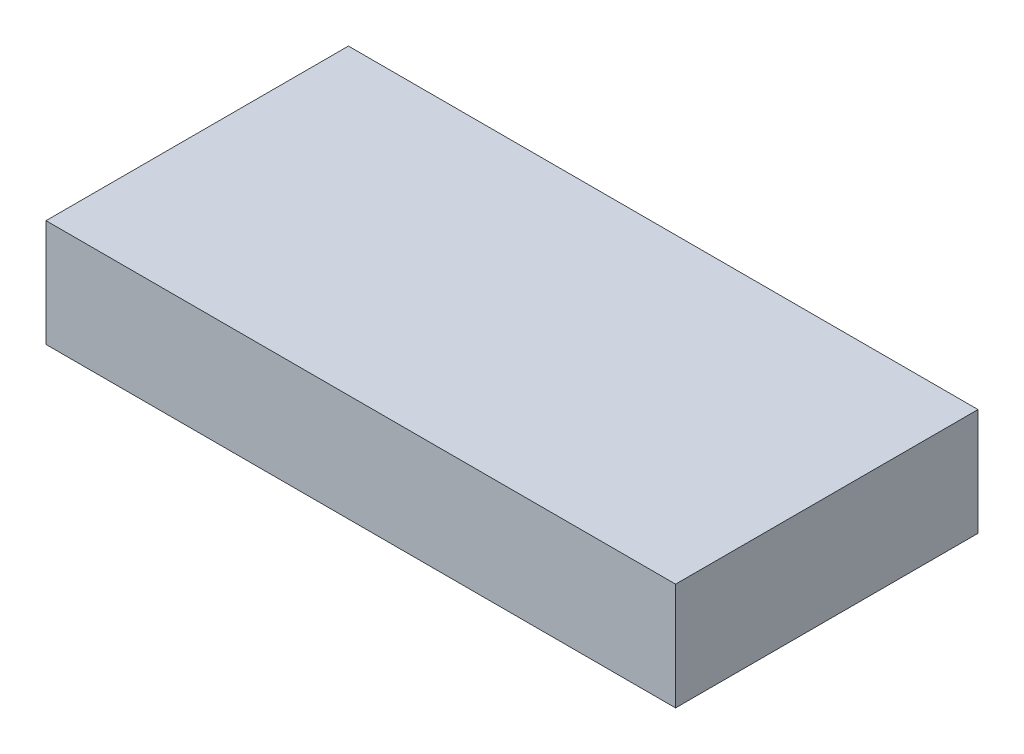
SolidWorks part; units mm, degrees
ref_plane "Front Plane" through (0, 0, 0) normal (0, 0, 1) x (1, 0, 0)
ref_plane "Top Plane" through (0, 0, 0) normal (0, 1, 0) x (1, 0, 0)
ref_plane "Right Plane" through (0, 0, 0) normal (1, 0, 0) x (0, 0, -1)
sketch "Sketch1" plane through (0, 0, 0) normal (0, 1, 0) x (1, 0, 0)
  line L1 (572.5, -275) -> (-572.5, -275)
  line L2 (572.5, -275) -> (572.5, 275)
  line L3 (572.5, 275) -> (-572.5, 275)
  line L4 (-572.5, -275) -> (-572.5, 275)
  line L5 (572.5, -275) -> (-572.5, 275) construction
  line L6 (572.5, 275) -> (-572.5, -275) construction
  point P0 (0, 0)
  dimension "D1" = 1145
  dimension "D2" = 550
extrude "Boss-Extrude1" add sketch "Sketch1" along normal blind 195
